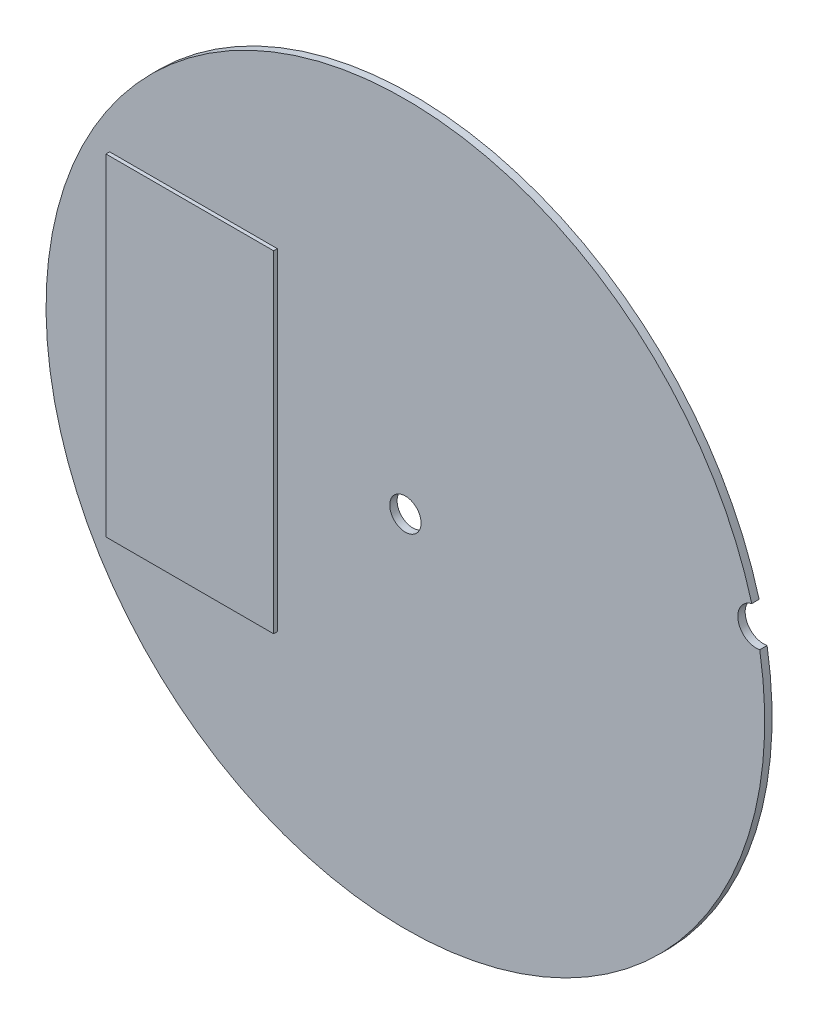
SolidWorks part; units mm, degrees
ref_plane "Plan de face" through (0, 0, 0) normal (0, 0, 1) x (1, 0, 0)
ref_plane "Plan de dessus" through (0, 0, 0) normal (0, 1, 0) x (1, 0, 0)
ref_plane "Plan de droite" through (0, 0, 0) normal (1, 0, 0) x (0, 0, -1)
sketch "Esquisse1" plane through (0, 0, 0) normal (0, 0, 1) x (1, 0, 0)
  line L0 (0, 0) -> (19.5, 0) construction
  line L1 (0, 19.5) -> (0, 0) construction
  line L2 (-6.7, -3.3481) -> (-6.7, 3.3481) construction
  line L3 (-11.5, -4.5) -> (-11.5, 4.5) construction
  line L4 (-14.5, -4.5) -> (-14.5, 4.5)
  line L5 (-8.5, -4.5) -> (-8.5, 4.5)
  line L6 (-11.5, 0) -> (0, 0) construction
  line L7 (0, 0) -> (19.0378, 4.2206) construction
  arc A0 (18.7964, 5.191) -> (19.2291, 3.239) centre (0, 0) ccw
  circle A4 centre (0, 0) radius 0.85
  arc A5 (18.7964, 5.191) -> (19.2291, 3.239) centre (19.0378, 4.2206) ccw
  arc A6 (-14.5, -4.5) -> (-8.5, -4.5) centre (-11.5, -4.5) ccw
  arc A7 (-8.5, 4.5) -> (-14.5, 4.5) centre (-11.5, 4.5) ccw
  point P5 (8.234, -1.9)
  point P6 (-7.9, -3)
  point P11 (-11.5, 0)
  point P20 (-11.5, 0)
  point P22 (18.7035, 9.8546)
  point P23 (16.556, 10.7262)
  point P24 (0, 0)
  dimension "D1" = 39
  dimension "D10" = 1.7
  dimension "D8" = 1
  dimension "D2" = 1.9
  dimension "D3" = 3
  dimension "D4" = 7.9
  dimension "D5" = 8.234
  dimension "D6" = 6
  dimension "D7" = 9
  dimension "D11" = 1.8
  dimension "D9" = 12.5
  dimension "D12" = 19.5
  dimension "D13" = 19.5
extrude "Boss.-Extru.1" add sketch "Esquisse1" along normal blind 0.4
sketch "Esquisse2" plane through (0, 0, 0.4) normal (0, 0, 1) x (1, 0, 0)
  line L0 (-11.5, -7.5) -> (-11.5, 7.5) construction
  line L1 (-16.05, 9) -> (-6.95, 9)
  line L2 (-16.05, 9) -> (-16.05, -9)
  line L3 (-16.05, -9) -> (-6.95, -9)
  line L4 (-6.95, 9) -> (-6.95, -9)
  line L5 (-16.05, 9) -> (-6.95, -9) construction
  line L6 (-16.05, -9) -> (-6.95, 9) construction
  arc A0 (-14.5, -4.5) -> (-8.5, -4.5) centre (-11.5, -4.5) ccw construction
  arc A1 (-8.5, 4.5) -> (-14.5, 4.5) centre (-11.5, 4.5) ccw construction
  point P0 (-11.5, 0)
  dimension "D1" = 9.1
  dimension "D2" = 18
extrude "Boss.-Extru.2" add sketch "Esquisse2" along normal blind 0.2
equation "\"D13@Esquisse1\"=\"D12@Esquisse1\""
